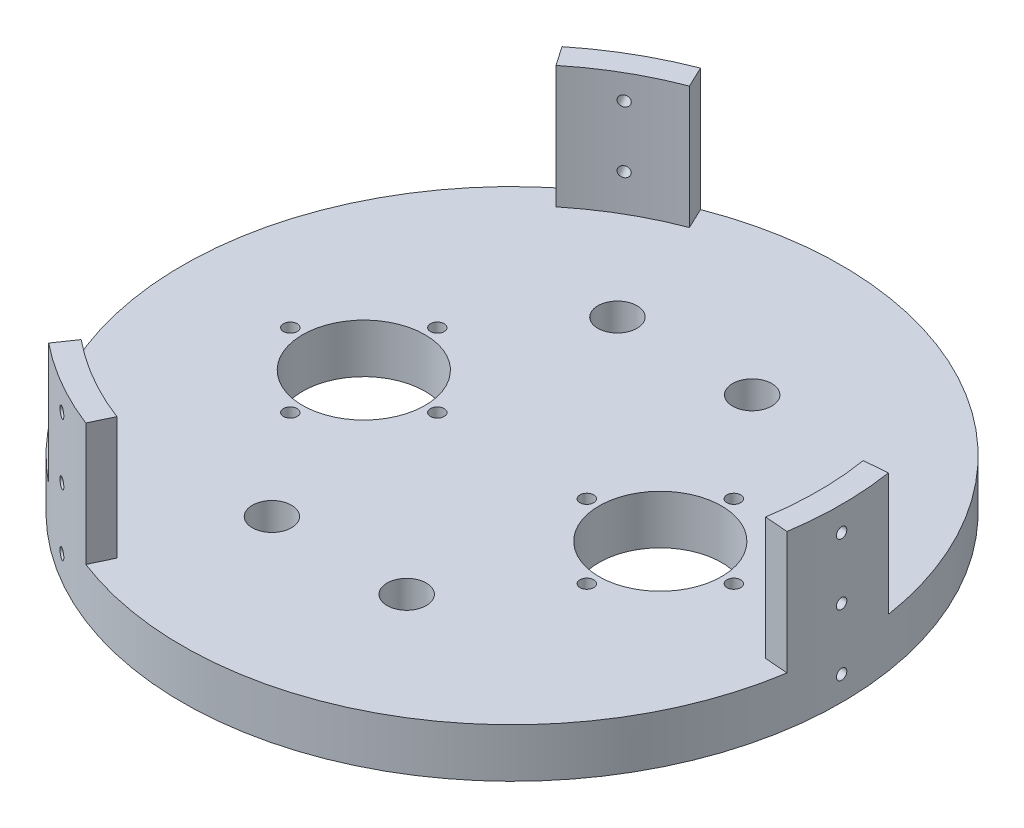
SolidWorks part; units mm, degrees
material "6061-T6 (SS)"
ref_plane "Front" through (0, 0, 0) normal (0, 0, 1) x (1, 0, 0)
ref_plane "Top" through (0, 0, 0) normal (0, 1, 0) x (1, 0, 0)
ref_plane "Right" through (0, 0, 0) normal (1, 0, 0) x (0, 0, -1)
sketch "Sketch1" plane through (0, 0, 0) normal (0, 1, 0) x (1, 0, 0)
  line L1 (0, 0) -> (127.635, 0)
  line L2 (0, 0) -> (0, 127.635)
  line L3 (0, 127.635) -> (127.635, 127.635)
  line L4 (127.635, 0) -> (127.635, 127.635)
  dimension "D1" = 127.635
  dimension "D2" = 127.635
extrude "Main Plate" add sketch "Sketch1" along normal blind 12.7
sketch "Sketch9" plane through (0, 12.7, 0) normal (0, 1, 0) x (1, 0, 0)
  circle A0 centre (63.8175, 63.8175) radius 85.725
  dimension "D1" = 171.45
extrude "Boss-Extrude1" add sketch "Sketch9" against normal up to surface (12.7 mm away) contours A0 up to face at (63.8175, 0, -63.8175)
sketch "Sketch10" plane through (0, 12.7, 0) normal (0, 1, 0) x (1, 0, 0)
  circle A0 centre (63.8175, 63.8175) radius 95.25
  circle A1 centre (63.8175, 63.8175) radius 85.4075
  dimension "D1" = 170.815
  dimension "D2" = 190.5
extrude "Cut-Extrude1" cut sketch "Sketch10" against normal blind 167.64 contours A0 | A1
sketch "Sketch14" plane through (0, 12.7, 0) normal (0, 1, 0) x (1, 0, 0)
  line L0 (201.1692, 63.8175) -> (-73.4523, 63.8175) construction
ref_plane "Plane1" through (0, 0, -63.8175) normal (0, 0, -1) x (-1, 0, 0)
ref_plane "Plane3" through (0, 6.35, 0) normal (0, 1, 0) x (1, 0, 0)
ref_plane "Plane2" through (-21.59, 0, 0) normal (-1, 0, 0) x (0, 0, 1)
sketch "Sketch18" plane through (0, 6.35, 0) normal (0, 1, 0) x (1, 0, 0)
  circle A0 centre (63.8175, 63.8175) radius 85.4075
  circle A1 centre (63.8175, 63.8175) radius 79.375
  circle A4 centre (63.8175, 63.8175) radius 85.4075 construction
  dimension "D1" = 158.75
extrude "Boss-Extrude2" add sketch "Sketch18" along normal blind 38.1
sketch "Sketch20" plane through (0, 12.7, 0) normal (0, 1, 0) x (1, 0, 0)
  line L0 (63.8175, 143.1925) -> (63.8175, -15.5575) construction
  line L1 (-15.5575, 63.8175) -> (143.1925, 63.8175) construction
  line L2 (63.8175, 63.8175) -> (-15.5575, -73.664) construction
  circle A0 centre (63.8175, 63.8175) radius 79.375 construction
  dimension "D1" = 30
ref_plane "Plane5" through (-15.5575, 12.7, 73.664) normal (-0.5, 0, 0.866) x (0.866, 0, 0.5)
sketch "Sketch15" plane through (166.2216, 0, 178.6143) normal (0.5, 0, -0.866) x (-0.866, 0, -0.5)
  line L3 (289.2754, 44.45) -> (130.5254, 44.45) construction
  line L4 (124.4929, 0) -> (295.3079, 0) construction
  line L6 (278.6412, 12.7) -> (141.1597, 12.7) construction
  circle A0 centre (209.9004, 22.225) radius 1.3526
  circle A1 centre (209.9004, 38.1) radius 1.3526
  circle A2 centre (209.9004, 6.35) radius 1.3526
  point P16 (209.9004, 12.7)
  dimension "D1" = 2.7051
  dimension "D2" = 15.875
  dimension "D3" = 2.7051
  dimension "D4" = 2.7051
  dimension "D5" = 6.35
  dimension "D6" = 6.35
  dimension "D7" = 0
extrude "Cut-Extrude3" cut sketch "Sketch15" along normal blind 88.9
pattern_circular "CirPattern1" count 3 over 360 about axis through (63.8175, -154.94, -63.8175) along (0, 1, 0) of "Cut-Extrude3" reverse direction yes
ref_plane "Plane4" through (63.8175, 0, 0) normal (-1, 0, 0) x (0, 0, 1)
sketch "Sketch21" plane through (0, 12.7, 0) normal (0, 1, 0) x (1, 0, 0)
  line L1 (-15.5575, 63.8175) -> (143.1925, 63.8175) construction
  line L2 (102.235, 63.8175) -> (102.235, 100.651) construction
  line L3 (63.8175, 87.3125) -> (63.8175, -87.3125) construction
  circle A0 centre (102.235, 63.8175) radius 15.875
  circle A1 centre (102.235, 82.8675) radius 1.778
  circle A2 centre (25.4, 63.8175) radius 15.875
  circle A3 centre (121.285, 63.8175) radius 1.778
  circle A4 centre (102.235, 44.7675) radius 1.778
  circle A5 centre (83.185, 63.8175) radius 1.778
  circle A6 centre (25.4, 82.8675) radius 1.778
  circle A7 centre (6.35, 63.8175) radius 1.778
  circle A8 centre (25.4, 44.7675) radius 1.778
  circle A9 centre (44.45, 63.8175) radius 1.778
  dimension "D1" = 31.75
  dimension "D2" = 3.556
  dimension "D6" = 19.05
  dimension "D3" = 19.05
  dimension "D4" = 76.835
  dimension "D7" = 19.05
  dimension "D5" = 4
extrude "CO2 Mounts" cut sketch "Sketch21" against normal through all
sketch "Sketch22" plane through (0, 12.7, 0) normal (0, 1, 0) x (1, 0, 0)
  line L0 (63.8175, 87.3125) -> (63.8175, -87.3125) construction
  line L1 (87.3125, 63.8175) -> (-87.3125, 63.8175) construction
  circle A0 centre (46.355, 108.585) radius 5.08
  circle A1 centre (81.28, 108.585) radius 5.08
  circle A2 centre (81.28, 19.05) radius 5.08
  circle A3 centre (46.355, 19.05) radius 5.08
  dimension "D1" = 10.16
  dimension "D2" = 34.925
  dimension "D3" = 89.535
extrude "Cut-Extrude5" cut sketch "Sketch22" against normal through all
sketch "Sketch23" plane through (0, 12.7, 0) normal (0, 1, 0) x (1, 0, 0)
  line L0 (13.6787, 125.352) -> (7.5523, 134.2379)
  line L1 (15.1867, 11.8815) -> (13.6787, 2.283) construction
  line L3 (-15.5575, 63.8175) -> (143.1925, 63.8175) construction
  line L4 (63.8175, 143.1925) -> (63.8175, -15.5575) construction
  line L5 (-15.5575, 63.8175) -> (143.1925, 63.8175)
  line L6 (63.8175, 143.1925) -> (63.8175, -15.5575)
  line L7 (13.6787, 2.283) -> (6.9592, -7.4631)
  line L8 (-19.2671, 125.3206) -> (-48.797, 60.3978)
  line L9 (-48.797, 60.3978) -> (-9.8843, 7.0525)
  line L10 (-9.8843, 7.0525) -> (6.9592, -7.4631)
  line L11 (24.1345, -4.9259) -> (13.6787, 2.283) construction
  line L14 (7.5523, 134.2379) -> (-19.2671, 125.3206)
  line L15 (24.1345, 132.5609) -> (13.6787, 125.352) construction
  line L28 (63.8175, 63.8175) -> (24.1345, -4.9259) construction
  line L29 (63.8175, 63.8175) -> (24.1345, 132.5609) construction
  line L30 (142.1773, 76.4717) -> (152.9359, 77.3344)
  line L31 (152.9359, 77.3344) -> (158.6231, 105.0193)
  line L32 (158.6231, 105.0193) -> (117.1632, 163.0543)
  line L33 (117.1632, 163.0543) -> (51.5085, 156.0277)
  line L34 (51.5085, 156.0277) -> (30.5159, 148.6985)
  line L35 (35.5964, 138.0062) -> (30.5159, 148.6985)
  line L36 (35.5964, -10.3712) -> (30.9643, -20.1198)
  line L37 (30.9643, -20.1198) -> (52.0965, -38.8874)
  line L38 (52.0965, -38.8874) -> (123.0863, -31.9996)
  line L39 (123.0863, -31.9996) -> (149.8284, 28.3723)
  line L40 (149.8284, 28.3723) -> (153.9775, 50.217)
  line L41 (142.1773, 51.1633) -> (153.9775, 50.217)
  circle A0 centre (63.8175, 63.8175) radius 79.375 construction
  arc A1 (13.6787, 2.283) -> (13.6787, 125.352) centre (63.8175, 63.8175) cw
  circle A3 centre (63.8175, 63.8175) radius 79.375
  arc A6 (35.5964, 138.0062) -> (142.1773, 76.4717) centre (63.8175, 63.8175) cw
  arc A7 (142.1773, 51.1633) -> (35.5964, -10.3712) centre (63.8175, 63.8175) cw
  circle A9 centre (63.8175, 63.8175) radius 79.375
  circle M15 centre (63.8175, 63.8175) radius 79.375
  dimension "D1" = 79.375
  dimension "D2" = 0
  dimension "D3" = 12.7
  dimension "D4" = 90
  dimension "D5" = 12.7
  dimension "D6" = 90
  dimension "D8" = 60.004
  dimension "D9" = 60.004
  dimension "D7" = 3
extrude "Cut-Extrude6" cut sketch "Sketch23" along normal blind 111.6 contours L9 L10 L7 L8 M15 | L34 L35 A6 L30 L31 L32 L33 | L40 L41 A7 L36 L37 L38 L39 region at (-18.2379, 12.7, -69.3048)
